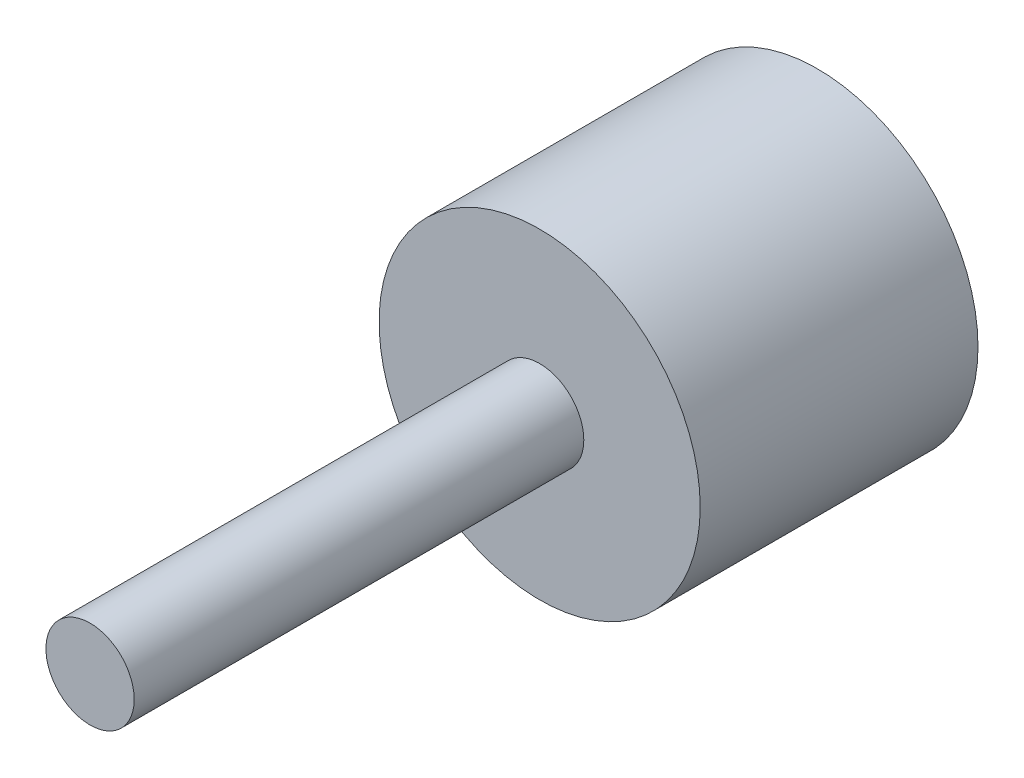
SolidWorks part; units mm, degrees
ref_plane "Plan de face" through (0, 0, 0) normal (0, 0, 1) x (1, 0, 0)
ref_plane "Plan de dessus" through (0, 0, 0) normal (0, 1, 0) x (1, 0, 0)
ref_plane "Plan de droite" through (0, 0, 0) normal (1, 0, 0) x (0, 0, -1)
sketch "Esquisse1" plane through (0, 0, 0) normal (0, 0, 1) x (1, 0, 0)
  circle A0 centre (0, 0) radius 10
  dimension "D1" = 20
extrude "Boss.-Extru.1" add sketch "Esquisse1" along normal blind 17.3
sketch "Esquisse2" plane through (0, 0, 17.3) normal (0, 0, 1) x (1, 0, 0)
  circle A0 centre (0, 0) radius 2.75
  dimension "D1" = 5.5
extrude "Boss.-Extru.2" add sketch "Esquisse2" along normal blind 28
sketch "Esquisse3" plane through (0, 0, 0) normal (0, 0, -1) x (-1, 0, 0)
  circle A0 centre (0, 0) radius 6
  dimension "D1" = 12
extrude "Boss.-Extru.3" add sketch "Esquisse3" along normal blind 2.7
fillet "Congé2" radius 6 1 edges at (-6, 0, -2.7)
